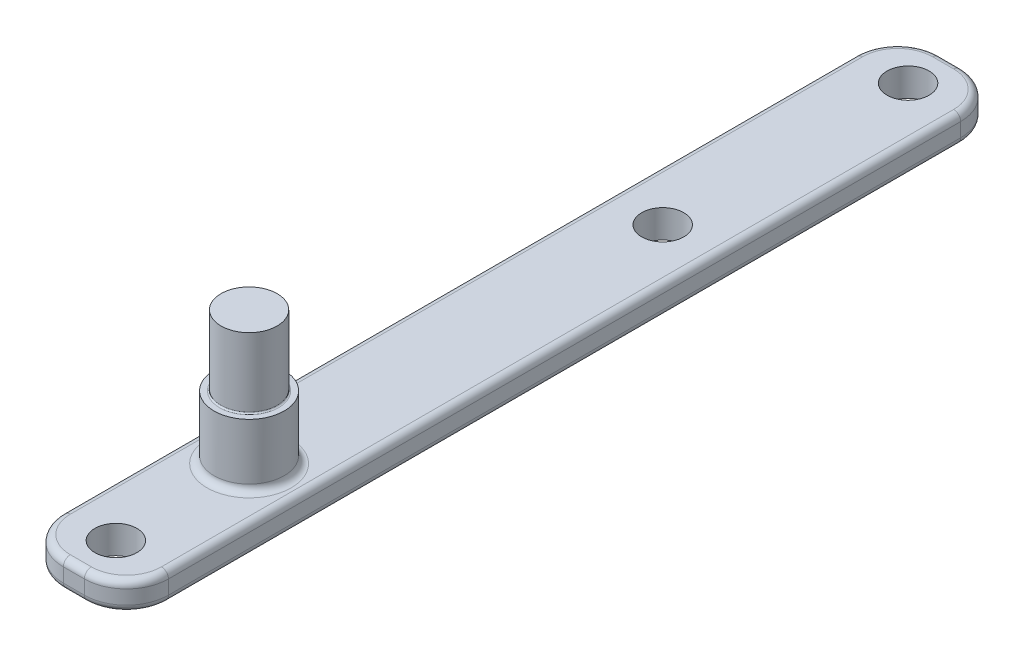
SolidWorks part; units mm, degrees
ref_plane "Front Plane" through (0, 0, 0) normal (0, 0, 1) x (1, 0, 0)
ref_plane "Top Plane" through (0, 0, 0) normal (0, 1, 0) x (1, 0, 0)
ref_plane "Right Plane" through (0, 0, 0) normal (1, 0, 0) x (0, 0, -1)
ref_axis "X-Axis" through (88.99, 0, 0) along (-1, 0, 0)
ref_axis "Y-Axis" through (0, 0, -88.99) along (0, 0, 1)
ref_axis "Z-Axis" through (0, -55, 0) along (0, 1, 0)
sketch "Sketch1" plane through (0, 0, 0) normal (0, 1, 0) x (1, 0, 0)
  line L0 (0, 88.99) -> (0, -88.99) construction
  line L2 (-7.5, 45) -> (-7.5, -45)
  line L3 (-7.5, -45) -> (7.5, -45)
  line L4 (7.5, 45) -> (7.5, -45)
  line L5 (88.99, 0) -> (-88.99, 0) construction
  line L6 (-7.5, 45) -> (-7.5, 80)
  line L7 (-7.5, 80) -> (7.5, 80)
  line L8 (7.5, 80) -> (7.5, 45)
  circle A0 centre (0, 39) radius 3
  circle A1 centre (0, -39) radius 3
  circle A3 centre (0, 74) radius 3
  point P4 (0, -45)
  point P7 (7.5, 0)
  dimension "D3" = 6
  dimension "D5" = 6
  dimension "D9" = 6
  dimension "D1" = 15
  dimension "D2" = 6
  dimension "D4" = 180
  dimension "D6" = 6
  dimension "D7" = 35
  dimension "D8" = 45
  dimension "D10" = 6
extrude "Boss-Extrude1" add sketch "Sketch1" along normal blind 4
sketch "Sketch2" plane through (0, 4, 0) normal (0, 1, 0) x (1, 0, 0)
  line L0 (0, 88.99) -> (0, -88.99) construction
  line L1 (-7.5, -45) -> (7.5, -45) construction
  circle A0 centre (0, -20) radius 5
  dimension "D1" = 10
  dimension "D2" = 25
extrude "Boss-Extrude2" add sketch "Sketch2" along normal blind 9
sketch "Sketch3" plane through (0, 13, 0) normal (0, 1, 0) x (1, 0, 0)
  circle A0 centre (0, -20) radius 4
  dimension "D1" = 8
extrude "Boss-Extrude3" add sketch "Sketch3" along normal blind 10
fillet "Fillet1" radius 1 1 edges at (0, 4, 15)
fillet "Fillet2" radius 6 4 edges at (-7.5, 2, 45) (7.5, 2, 45) (-7.5, 2, -80) (7.5, 2, -80)
fillet "Fillet3" radius 1 16 edges at (5.7426, 0, 43.2426) (0, 0, 45) (-5.7426, 0, 43.2426) (-7.5, 0, -17.5) (5.7426, 4, 43.2426) (0, 4, 45) (-5.7426, 4, 43.2426) (-7.5, 4, -17.5) (7.5, 0, -17.5) (7.5, 4, -17.5) (-5.7426, 0, -78.2426) (0, 0, -80) (5.7426, 0, -78.2426) (-5.7426, 4, -78.2426) (0, 4, -80) (5.7426, 4, -78.2426)
fillet "Fillet4" radius 0.2 1 edges at (0, 13, 24)
sketch "Sketch6" plane through (0, 4, 0) normal (0, 1, 0) x (1, 0, 0)
  line L0 (0, 88.99) -> (0, -88.99) construction
  line L1 (-4, 75) -> (4, 75)
  line L2 (-4, 75) -> (-4, 63)
  line L3 (-4, 63) -> (4, 63)
  line L4 (4, 75) -> (4, 63)
  line L5 (1.5, 79) -> (-1.5, 79) construction
  point P4 (0, 63)
  point P7 (0, 75)
  dimension "D1" = 8
  dimension "D2" = 12
  dimension "D3" = 4
extrude "Boss-Extrude4" [suppressed] add sketch "Sketch6" along normal blind 20
sketch "Sketch7" [suppressed] plane through (4, 0, 0) normal (1, 0, 0) x (0, 0, -1)
  line L2 (68, 6) -> (80, 6) construction
  circle A0 centre (74, 16) radius 3
  point P9 (74, 6)
  dimension "D2" = 6
  dimension "D1" = 10
extrude "Cut-Extrude1" [suppressed] cut sketch "Sketch7" against normal blind 20
